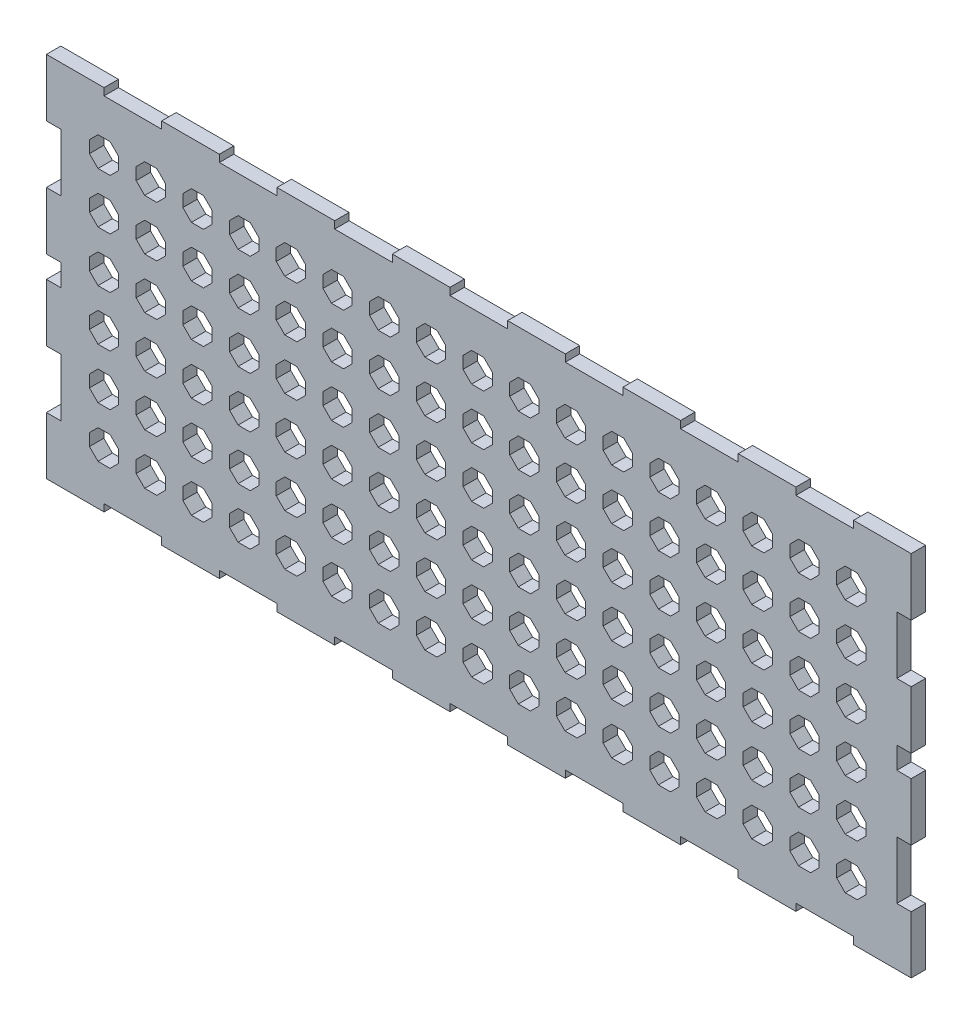
SolidWorks part; units mm, degrees
material "Oak"
ref_plane "Front Plane" through (0, 0, 0) normal (0, 0, 1) x (1, 0, 0)
ref_plane "Top Plane" through (0, 0, 0) normal (0, 1, 0) x (1, 0, 0)
ref_plane "Right Plane" through (0, 0, 0) normal (1, 0, 0) x (0, 0, -1)
sketch "Sketch1" plane through (0, 0, 0) normal (0, 0, 1) x (1, 0, 0)
  line L1 (0, 0) -> (190.5, 0)
  line L2 (0, 0) -> (0, -80.9625)
  line L3 (0, -80.9625) -> (190.5, -80.9625)
  line L4 (190.5, 0) -> (190.5, -80.9625)
extrude "Boss-Extrude1" add sketch "Sketch1" along normal blind 3.175
ref_plane "Plane1" through (95.25, 0, 0) normal (1, 0, 0) x (0, 0, -1)
sketch "Sketch2" plane through (0, 0, 3.175) normal (0, 0, 1) x (1, 0, 0)
  line L0 (0, 0) -> (0, -80.9625) construction
  line L1 (0, -12.7) -> (3.175, -12.7)
  line L2 (0, -12.7) -> (0, -25.4)
  line L3 (0, -25.4) -> (3.175, -25.4)
  line L4 (3.175, -12.7) -> (3.175, -25.4)
extrude "Cut-Extrude1" cut sketch "Sketch2" against normal through all
sketch "Sketch3" plane through (0, 0, 3.175) normal (0, 0, 1) x (1, 0, 0)
  line L0 (0, -25.4) -> (0, -80.9625) construction
  line L1 (0, -38.1) -> (3.175, -38.1)
  line L2 (0, -38.1) -> (0, -42.926)
  line L3 (0, -42.926) -> (3.175, -42.926)
  line L4 (3.175, -38.1) -> (3.175, -42.926)
extrude "Cut-Extrude2" cut sketch "Sketch3" against normal through all
pattern_linear "LPattern1" count 2 spacing 42.926 along (0, -1, 0) of "Cut-Extrude1"
sketch "Sketch4" plane through (0, 0, 3.175) normal (0, 0, 1) x (1, 0, 0)
  line L0 (190.5, 0) -> (0, 0) construction
  line L1 (12.7, 0) -> (25.4, 0)
  line L2 (12.7, 0) -> (12.7, -1.5875)
  line L3 (12.7, -1.5875) -> (25.4, -1.5875)
  line L4 (25.4, 0) -> (25.4, -1.5875)
extrude "Cut-Extrude3" cut sketch "Sketch4" against normal through all
pattern_linear "LPattern2" count 7 spacing 25.4 along (1, 0, 0) of "Cut-Extrude3"
ref_plane "Plane4" through (0, -40.4812, 0) normal (0, 1, 0) x (1, 0, 0)
mirror "Mirror1" about plane through (0, -40.4812, 0) normal (0, 1, 0) of "LPattern2", "Cut-Extrude3"
mirror "Mirror2" about plane through (95.25, 0, 0) normal (1, 0, 0) of "LPattern1", "Cut-Extrude2", "Cut-Extrude1"
hole_wizard "Hole1" [suppressed] positions "Sketch6" profile "Sketch5" legacy
sketch "Sketch6" plane through (0, 0, 3.175) normal (0, 0, 1) x (1, 0, 0)
  point P0 (12.7, -12.7)
sketch "Sketch5" plane through (12.7, -12.7, 3.175) normal (1, 0, 0) x (0, -1, 0)
  line L0 (0, 0) -> (0, 3.175)
  line L1 (0, 3.175) -> (3.175, 3.175)
  line L2 (3.175, 3.175) -> (3.175, 0)
  line L3 (3.175, 0) -> (0, 0)
  line L4 (0, 110) -> (0, -10) construction
  dimension "Diameter" = 6.35
  dimension "Depth" = 3.175
pattern_linear "LPattern3" [suppressed] count 14 spacing 12.7 count 6 spacing 11.176
sketch "Sketch7" plane through (0, 0, 3.175) normal (0, 0, 1) x (1, 0, 0)
  line L1 (15.9194, -11.5352) -> (14.0335, -9.6493)
  line L2 (14.0335, -9.6493) -> (11.3665, -9.6493)
  line L3 (11.3665, -9.6493) -> (9.4806, -11.5352)
  line L4 (9.4806, -11.5352) -> (9.4806, -14.2022)
  line L5 (9.4806, -14.2022) -> (11.3665, -16.0881)
  line L6 (11.3665, -16.0881) -> (14.0335, -16.0881)
  line L7 (14.0335, -16.0881) -> (15.9194, -14.2022)
  line L8 (15.9194, -14.2022) -> (15.9194, -11.5352)
  circle A0 centre (12.7, -12.8687) radius 3.4846 construction
extrude "Cut-Extrude4" cut sketch "Sketch7" against normal through all
pattern_linear "LPattern5" count 17 spacing 10.287 along (1, 0, 0) count 6 spacing 11.176 along (0, -1, 0) of "Cut-Extrude4"
